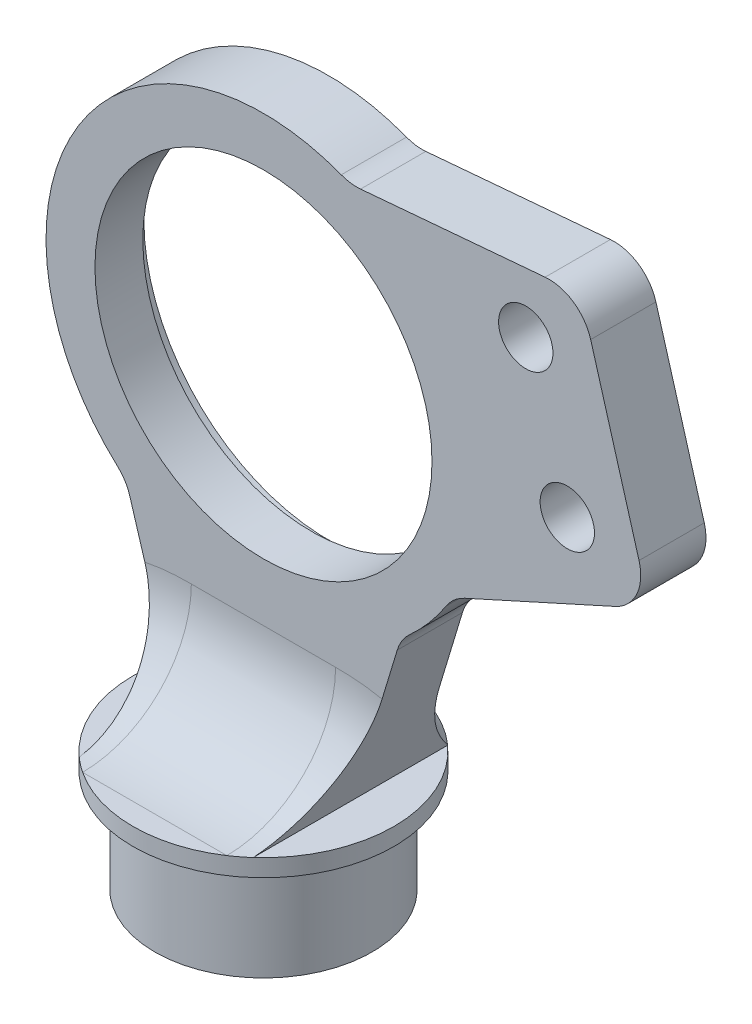
SolidWorks part; units mm, degrees
ref_plane "Front Plane" through (0, 0, 0) normal (0, 0, 1) x (1, 0, 0)
ref_plane "Top Plane" through (0, 0, 0) normal (0, 1, 0) x (1, 0, 0)
ref_plane "Right Plane" through (0, 0, 0) normal (1, 0, 0) x (0, 0, -1)
sketch "草图1" plane through (0, 0, 0) normal (0, 0, 1) x (1, 0, 0)
  line L0 (-24.0723, 20.5588) -> (-21.7527, 12.9038)
  line L11 (-24.0723, 20.5588) -> (-11.4331, 20.5588) construction
  line L12 (-11.4331, 20.5588) -> (-13.7527, 12.9038)
  line L13 (-21.7527, 12.9038) -> (-13.7527, 12.9038)
  line L17 (-13.7682, 37.4807) -> (-3.162, 38.3996)
  line L18 (-3.162, 38.3996) -> (0, 27.4688)
  line L19 (0, 27.4688) -> (-9.058, 23.3689)
  arc A5 (-11.4331, 20.5588) -> (-9.058, 23.3689) centre (-17.7527, 28.3088) ccw
  circle A9 centre (-17.7527, 28.3088) radius 7.75
  circle A10 centre (-17.7527, 28.3088) radius 14 construction
  circle A11 centre (-3.7812, 29.2018) radius 1.25
  circle A12 centre (-5.6903, 35.4151) radius 1.25
  arc A13 (-13.7682, 37.4807) -> (-24.0723, 20.5588) centre (-17.7527, 28.3088) ccw
  point P0 (-17.7527, 12.9038)
  dimension "D5" = 10
  dimension "D6" = 2.5
  dimension "D4" = 6.5
  dimension "D2" = 15.5
  dimension "D1" = 8
  dimension "D3" = 28
  dimension "D7" = 2.5
extrude "凸台-拉伸3" add sketch "草图1" along normal blind 3
sketch "草图7" plane through (0, 12.9038, 0) normal (0, -1, 0) x (1, 0, 0)
  line L0 (-21.7527, 3) -> (-13.7527, 3) construction
  circle A0 centre (-17.7527, 3) radius 5
  dimension "D1" = 10
extrude "凸台-拉伸8" add sketch "草图7" along normal blind 5.5
sketch "草图8" plane through (0, 12.9038, 0) normal (0, 1, 0) x (1, 0, 0)
  circle A0 centre (-17.7527, -3) radius 6
  dimension "D1" = 12
extrude "凸台-拉伸9" add sketch "草图8" against normal blind 0.8
fillet "圆角1" radius 5 2 edges at (-17.7527, 12.9038, 0) (-17.7527, 12.9038, 3)
sketch "草图9" plane through (0, 7.4038, 0) normal (0, -1, 0) x (1, 0, 0)
  circle A0 centre (-17.7527, 3) radius 3.15
  dimension "D1" = 6.3
extrude "切除-拉伸4" cut sketch "草图9" against normal blind 3
sketch "草图12" plane through (0, 0, 0) normal (0, 0, -1) x (-1, 0, 0)
  circle A0 centre (17.7527, 28.3088) radius 8.5
  dimension "D1" = 17
extrude "切除-拉伸6" cut sketch "草图12" against normal blind 0.8
fillet "圆角2" radius 2 6 edges at (-24.0723, 20.5588, 1.5) (-11.4331, 20.5588, 1.5) (-9.058, 23.3689, 1.5) (-13.7682, 37.4807, 1.5) (0, 27.4688, 1.5) (-3.162, 38.3996, 1.5)
